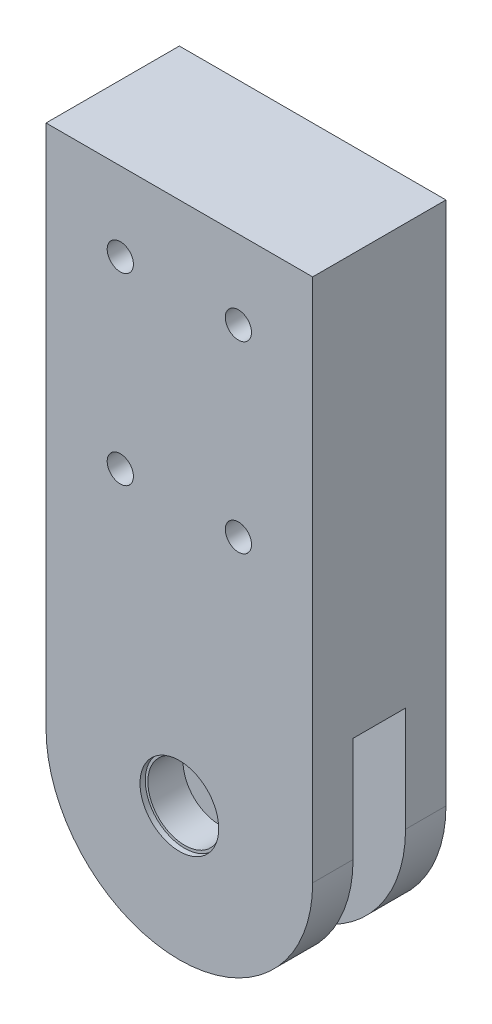
SolidWorks part; units mm, degrees
ref_plane "Front Plane" through (0, 0, 0) normal (0, 0, 1) x (1, 0, 0)
ref_plane "Top Plane" through (0, 0, 0) normal (0, 1, 0) x (1, 0, 0)
ref_plane "Right Plane" through (0, 0, 0) normal (1, 0, 0) x (0, 0, -1)
sketch "Sketch1" plane through (0, 0, 0) normal (0, 0, 1) x (1, 0, 0)
  line L0 (-25.4, 0) -> (-25.4, 100)
  line L1 (-25.4, 100) -> (25.4, 100)
  line L2 (25.4, 100) -> (25.4, 0)
  line L4 (-11.25, 85) -> (11.25, 85) construction
  line L5 (-11.25, 85) -> (-11.25, 50) construction
  line L6 (-11.25, 50) -> (11.25, 50) construction
  line L7 (11.25, 85) -> (11.25, 50) construction
  circle A0 centre (0, 0) radius 7
  arc A1 (-25.4, 0) -> (25.4, 0) centre (0, 0) ccw
  circle A2 centre (-11.25, 85) radius 2.5
  circle A3 centre (11.25, 85) radius 2.5
  circle A4 centre (11.25, 50) radius 2.5
  circle A5 centre (-11.25, 50) radius 2.5
  point P13 (0, 50)
  dimension "D1" = 14
  dimension "D4" = 5
  dimension "D2" = 50.8
  dimension "D3" = 100
  dimension "D5" = 35
  dimension "D6" = 15
  dimension "D7" = 22.5
extrude "Boss-Extrude1" add sketch "Sketch1" along normal blind 25.4
sketch "Sketch2" plane through (25.4, 0, 0) normal (1, 0, 0) x (0, 0, -1)
  line L0 (-25.4, -25.4) -> (0, -25.4) construction
  line L1 (-17.7, 20) -> (-7.7, 20)
  line L2 (-17.7, 20) -> (-17.7, -25.4)
  line L3 (-17.7, -25.4) -> (-7.7, -25.4)
  line L4 (-7.7, 20) -> (-7.7, -25.4)
  line L5 (-25.4, 0) -> (0, 0) construction
  point P8 (-12.7, 0)
  point P9 (-12.7, 20)
  dimension "D1" = 10
  dimension "D2" = 20
extrude "Cut-Extrude1" cut sketch "Sketch2" against normal through all
sketch "Sketch3" plane through (0, 0, 25.4) normal (0, 0, 1) x (1, 0, 0)
  circle A0 centre (0, 0) radius 7.5
  dimension "D1" = 15
extrude "Cut-Extrude2" cut sketch "Sketch3" against normal blind 1
sketch "Sketch4" plane through (0, 0, 0) normal (0, 0, -1) x (-1, 0, 0)
  circle A0 centre (0, 0) radius 7.5
  dimension "D1" = 15
extrude "Cut-Extrude3" cut sketch "Sketch4" against normal blind 1
